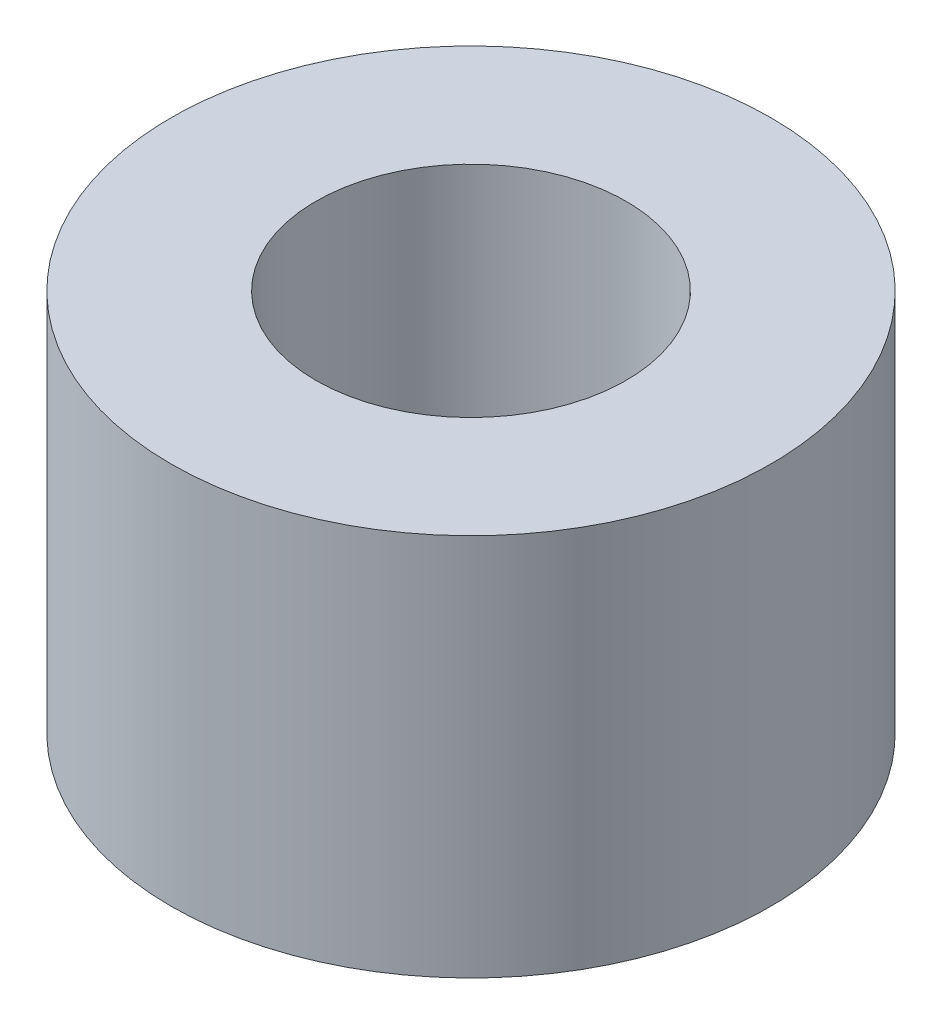
SolidWorks part; units mm, degrees
ref_plane "Front Plane" through (0, 0, 0) normal (0, 0, 1) x (1, 0, 0)
ref_plane "Top Plane" through (0, 0, 0) normal (0, 1, 0) x (1, 0, 0)
ref_plane "Right Plane" through (0, 0, 0) normal (1, 0, 0) x (0, 0, -1)
sketch "Sketch1" plane through (0, 0, 0) normal (0, 1, 0) x (1, 0, 0)
  circle A0 centre (0, 0) radius 15
  dimension "SLEEVE_OD" = 30
extrude "Boss-Extrude1" add sketch "Sketch1" along normal blind 19.1558
sketch "Sketch2" plane through (0, 0, 0) normal (0, 1, 0) x (1, 0, 0)
  circle A0 centre (0, 0) radius 7.7607
  dimension "BORE_D" = 15.5213
extrude "Cut-Extrude1" cut sketch "Sketch2" along normal through all
chamfer "Chamfer1" distance 2.7007 angle 60 rebuild error yes
